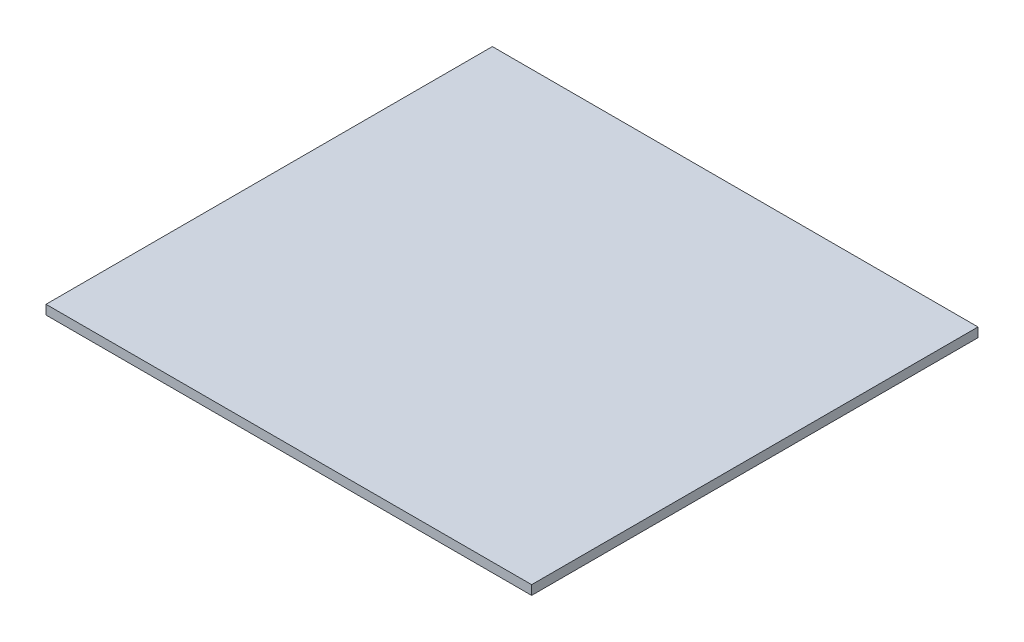
SolidWorks part; units mm, degrees
ref_plane "Alzado" through (0, 0, 0) normal (0, 0, 1) x (1, 0, 0)
ref_plane "Planta" through (0, 0, 0) normal (0, 1, 0) x (1, 0, 0)
ref_plane "Vista lateral" through (0, 0, 0) normal (1, 0, 0) x (0, 0, -1)
sketch "Croquis1" plane through (0, 0, 0) normal (0, 1, 0) x (1, 0, 0)
  line L1 (165, -151.655) -> (-165, -151.655)
  line L2 (165, -151.655) -> (165, 151.655)
  line L3 (165, 151.655) -> (-165, 151.655)
  line L4 (-165, -151.655) -> (-165, 151.655)
  line L5 (165, -151.655) -> (-165, 151.655) construction
  line L6 (165, 151.655) -> (-165, -151.655) construction
  point P0 (0, 0)
  dimension "D1" = 330
  dimension "D2" = 303.31
extrude "Saliente-Extruir2" add sketch "Croquis1" along normal blind 6.35
sketch "Croquis2" plane through (0, 6.35, 0) normal (0, 1, 0) x (1, 0, 0)
  line L0 (-165, 129.3909) -> (165, 129.3909) construction
  line L3 (-165, 151.655) -> (-165, -151.655) construction
  line L4 (165, -151.655) -> (165, 151.655) construction
sketch "Croquis3" plane through (0, 6.35, 0) normal (0, 1, 0) x (1, 0, 0)
  line L0 (-165, -151.655) -> (165, -151.655) construction
  line L1 (-165, 151.655) -> (-135.28, 151.655)
  line L2 (-165, 151.655) -> (-165, -151.655)
  line L3 (-165, -151.655) -> (-135.28, -151.655)
  line L4 (-135.28, 151.655) -> (-135.28, -151.655)
  line L5 (-165, -118.245) -> (165, -118.245) construction
  line L6 (165, -151.655) -> (165, 151.655) construction
  line L7 (-122.58, -147.8926) -> (-122.58, -88.5974) construction
  line L8 (-97.18, -151.655) -> (-97.18, -77.7371) construction
  line L9 (0, 151.655) -> (0, -151.655) construction
  line L10 (165, 151.655) -> (-165, 151.655) construction
  line L11 (-165, 0) -> (165, 0) construction
  circle A0 centre (-122.58, -118.245) radius 3.9687
  circle A1 centre (-122.58, -105.545) radius 3.9687
  circle A2 centre (-122.58, -130.945) radius 3.9687
  circle A3 centre (-71.78, -130.945) radius 3.9687
  circle A4 centre (-71.78, -118.245) radius 3.9687
  circle A5 centre (-71.78, -105.545) radius 3.9687
  circle A24 centre (122.58, 118.245) radius 3.9687
  circle A25 centre (122.58, 105.545) radius 3.9687
  circle A26 centre (122.58, 130.945) radius 3.9687
  circle A27 centre (71.78, 130.945) radius 3.9687
  circle A28 centre (71.78, 118.245) radius 3.9687
  circle A29 centre (71.78, 105.545) radius 3.9687
  point P16 (-122.58, -118.245)
  point P59 (122.58, 118.245)
  dimension "D3" = 12.7
  dimension "D4" = 7.9375
  dimension "D5" = 12.7
  dimension "D6" = 12.7
  dimension "D1" = 29.72
  dimension "D2" = 33.41
  dimension "D7" = 25.4
